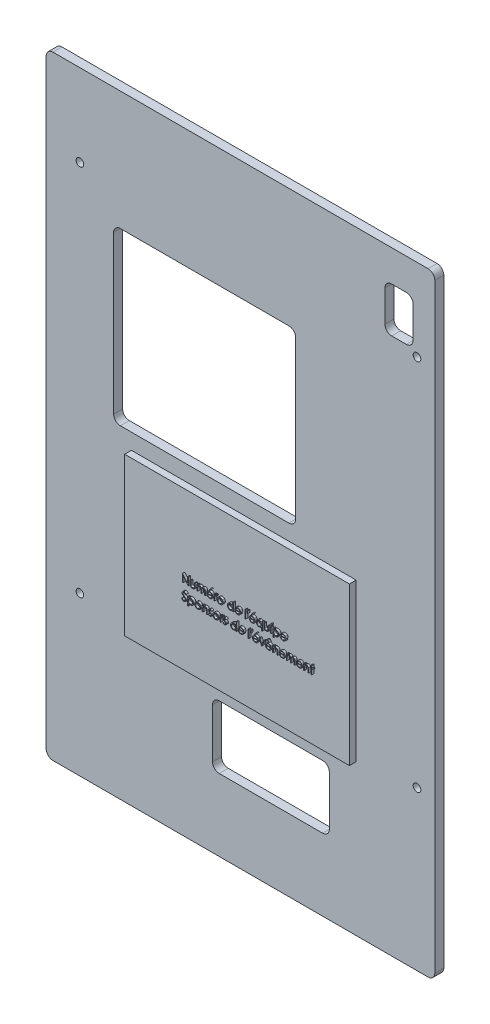
SolidWorks part; units mm, degrees
material "Verre"
ref_plane "Plan de face" through (0, 0, 0) normal (0, 0, 1) x (1, 0, 0)
ref_plane "Plan de dessus" through (0, 0, 0) normal (0, 1, 0) x (1, 0, 0)
ref_plane "Plan de droite" through (0, 0, 0) normal (1, 0, 0) x (0, 0, -1)
sketch "Esquisse1" plane through (0, 0, 0) normal (0, 0, 1) x (1, 0, 0)
  line L1 (0, 0) -> (172.93, 0)
  line L2 (0, 0) -> (0, 273)
  line L3 (0, 273) -> (172.93, 273)
  line L4 (172.93, 0) -> (172.93, 273)
  line L5 (74, 60) -> (126, 60)
  line L6 (74, 60) -> (74, 32)
  line L7 (74, 32) -> (126, 32)
  line L8 (126, 60) -> (126, 32)
  line L9 (30, 220) -> (111, 220)
  line L10 (30, 220) -> (30, 144)
  line L11 (30, 144) -> (111, 144)
  line L12 (111, 220) -> (111, 144)
  line L13 (163.25, 259) -> (150.75, 259)
  line L14 (163.25, 259) -> (163.25, 239)
  line L15 (163.25, 239) -> (150.75, 239)
  line L16 (150.75, 259) -> (150.75, 239)
  line L17 (163.25, 259) -> (150.75, 239) construction
  line L18 (163.25, 239) -> (150.75, 259) construction
  circle A0 centre (15, 236.5) radius 1.5
  circle A1 centre (165, 236.5) radius 1.5
  circle A2 centre (15, 70.5) radius 1.5
  circle A3 centre (165, 70.5) radius 1.5
  point P21 (157, 249)
  dimension "D5" = 3
  dimension "D8" = 3
  dimension "D11" = 3
  dimension "D22" = 3
  dimension "D25" = 12.5
  dimension "D1" = 172.93
  dimension "D2" = 273
  dimension "D3" = 36.5
  dimension "D4" = 15
  dimension "D6" = 7.93
  dimension "D7" = 36.5
  dimension "D9" = 70.5
  dimension "D10" = 15
  dimension "D12" = 74
  dimension "D13" = 52
  dimension "D14" = 28
  dimension "D15" = 32
  dimension "D16" = 30
  dimension "D17" = 81
  dimension "D18" = 144
  dimension "D19" = 76
  dimension "D20" = 7.93
  dimension "D21" = 70.5
  dimension "D23" = 15.93
  dimension "D24" = 24
  dimension "D26" = 20
extrude "Boss.-Extru.1" add sketch "Esquisse1" along normal blind 4
hole_wizard "Dégagement M31" positions "Esquisse2" profile "Esquisse3" hole size "M3" standard "ISO" end condition through all
sketch "Esquisse2" plane through (0, 0, 4) normal (0, 0, 1) x (1, 0, 0)
  point P0 (15, 236.5)
  point P3 (15, 70.5)
  point P6 (165, 236.5)
  point P9 (165, 70.5)
sketch "Esquisse3" plane through (15, 236.5, 4) normal (1, 0, 0) x (0, -1, 0)
  line L0 (0, 0) -> (0, 4)
  line L1 (0, 4) -> (1.7, 4)
  line L2 (1.7, 4) -> (1.7, 0)
  line L5 (1.7, 0) -> (0, 0)
  line L11 (0, -6.35) -> (0, 107.95) construction
  dimension "Diamètre du perçage jusqu'au prochain" = 3.4
  dimension "Profondeur du perçage jusqu'au prochain" = 4
fillet "Congé1" radius 3 16 edges at (0, 0, 2) (172.93, 0, 2) (126, 32, 2) (74, 32, 2) (126, 60, 2) (74, 60, 2) (111, 144, 2) (30, 144, 2) (111, 220, 2) (30, 220, 2) (172.93, 273, 2) (0, 273, 2) (163.25, 239, 2) (163.25, 259, 2) (150.75, 259, 2) (150.75, 239, 2)
sketch "Esquisse5" plane through (0, 0, 4) normal (0, 0, 1) x (1, 0, 0)
  line L0 (33, 144) -> (108, 144) construction
  line L1 (37.93, 137) -> (137.93, 137)
  line L2 (37.93, 137) -> (37.93, 67)
  line L3 (37.93, 67) -> (137.93, 67)
  line L4 (137.93, 137) -> (137.93, 67)
  line L5 (172.93, 3) -> (172.93, 270) construction
  line L6 (37.93, 102) -> (137.93, 102) construction
  dimension "D1" = 100
  dimension "D2" = 70
  dimension "D3" = 7
  dimension "D4" = 35
extrude "Boss.-Extru.3" add sketch "Esquisse5" along normal blind 3 contours L2 L3 L4 L1
sketch "Esquisse6" plane through (0, 0, 7) normal (0, 0, 1) x (1, 0, 0)
  text T0 "Numéro de l'équipe\r\nSponsors de l'évènement"
extrude "Boss.-Extru.4" add sketch "Esquisse6" along normal blind 1
